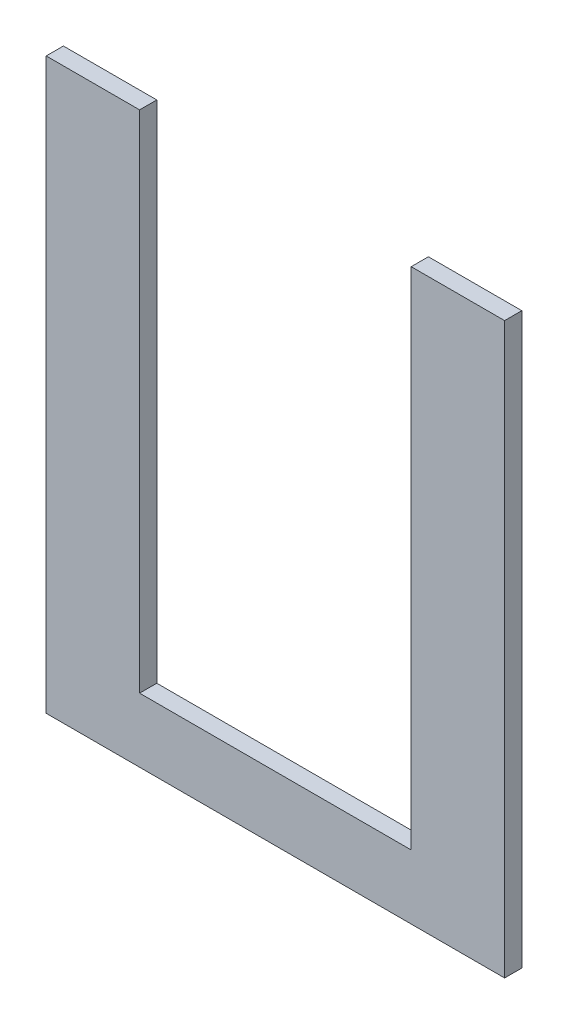
SolidWorks part; units mm, degrees
ref_plane "Front Plane" through (0, 0, 0) normal (0, 0, 1) x (1, 0, 0)
ref_plane "Top Plane" through (0, 0, 0) normal (0, 1, 0) x (1, 0, 0)
ref_plane "Right Plane" through (0, 0, 0) normal (1, 0, 0) x (0, 0, -1)
sketch "Sketch1" plane through (0, 0, 0) normal (0, 0, 1) x (1, 0, 0)
  line L0 (16.3, 99.357) -> (16.3, 11.2)
  line L1 (0, 0) -> (80, 0)
  line L2 (0, 0) -> (0, 99.357)
  line L3 (0, 99.357) -> (80, 99.357) construction
  line L4 (80, 0) -> (80, 99.357)
  line L5 (16.3, 11.2) -> (63.7, 11.2)
  line L6 (63.7, 11.2) -> (63.7, 99.357)
  line L7 (63.7, 99.357) -> (80, 99.357)
  line L8 (16.3, 99.357) -> (0, 99.357)
  line L9 (40, 99.357) -> (40, 0) construction
sketch "Sketch2" plane through (0, 0, 0) normal (0, 1, 0) x (1, 0, 0)
  line L1 (0, 0) -> (80, 0)
  line L2 (0, 0) -> (0, 3)
  line L3 (0, 3) -> (80, 3)
  line L4 (80, 0) -> (80, 3)
extrude "Boss-Extrude1" add sketch "Sketch1" against normal up to vertex (3 mm away) up to point (0, 0, -3)
